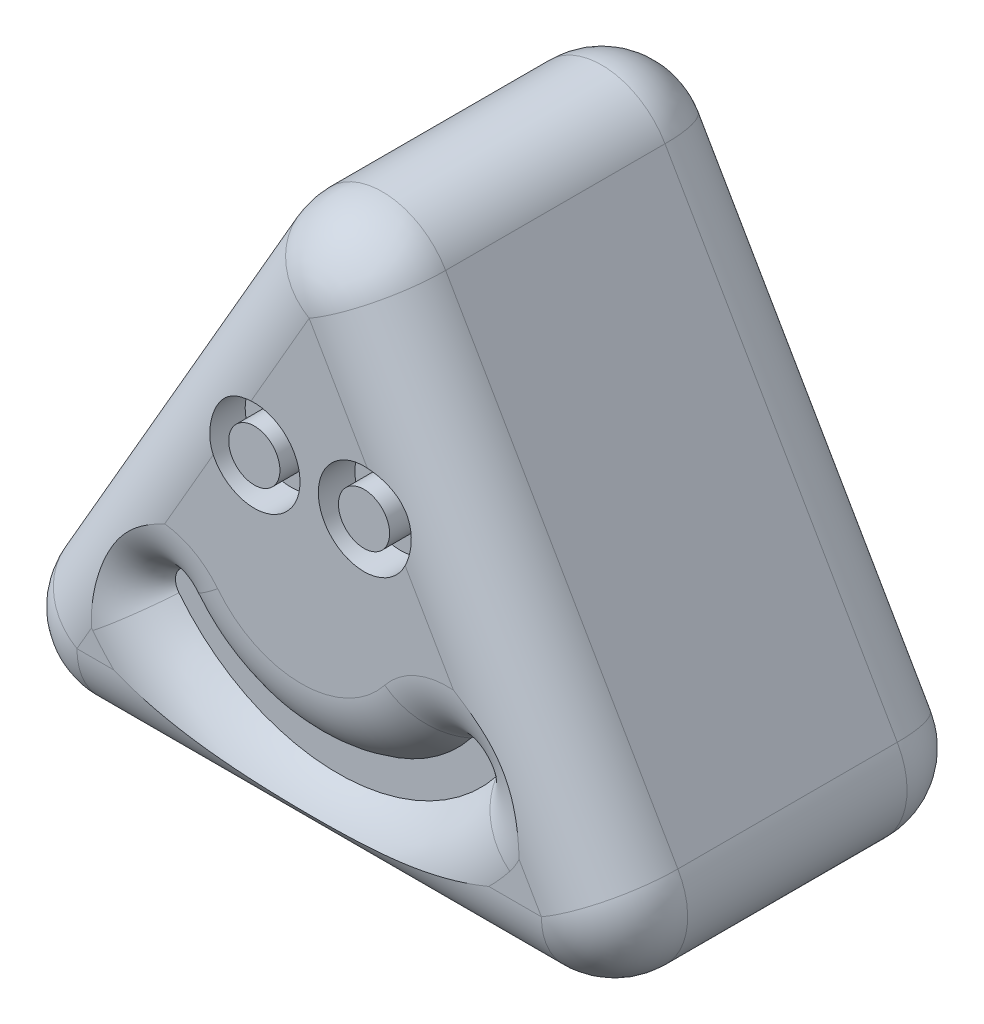
SolidWorks part; units mm, degrees
ref_plane "Front Plane" through (0, 0, 0) normal (0, 0, 1) x (1, 0, 0)
ref_plane "Top Plane" through (0, 0, 0) normal (0, 1, 0) x (1, 0, 0)
ref_plane "Right Plane" through (0, 0, 0) normal (1, 0, 0) x (0, 0, -1)
sketch "Sketch1" plane through (0, 0, 0) normal (0, 0, 1) x (1, 0, 0)
  line L0 (-9.815, -17) -> (9.815, -17)
  line L1 (9.815, -17) -> (0, 0)
  line L2 (0, 0) -> (-9.815, -17)
  point P4 (0, -17)
  dimension "D1" = 17
extrude "Boss-Extrude1" add sketch "Sketch1" along normal blind 10
sketch "Sketch2" plane through (0, 0, 10) normal (0, 0, 1) x (1, 0, 0)
  arc A0 (-4.2097, -13.0055) -> (3.7774, -13.0055) centre (-0.2162, -9.8526) ccw construction
  arc A1 (-4.5598, -13.2819) -> (4.1274, -13.2819) centre (-0.2162, -9.8526) ccw
  arc A2 (-3.8597, -12.7292) -> (3.4273, -12.7292) centre (-0.2162, -9.8526) ccw
  arc A3 (-3.8597, -12.7292) -> (-4.5598, -13.2819) centre (-4.2097, -13.0055) ccw
  arc A4 (4.1274, -13.2819) -> (3.4273, -12.7292) centre (3.7774, -13.0055) ccw
  point P3 (-0.2162, -14.9408)
extrude "Cut-Extrude1" cut sketch "Sketch2" against normal blind 1
fillet "Fillet1" radius 2 13 edges at (9.815, -17, 5) (0, 0, 5) (4.9075, -8.5, 0) (4.9075, -8.5, 10) (0, -17, 10) (-4.9075, -8.5, 10) (-0.2162, -15.3868, 10) (4.0537, -12.6555, 10) (-0.2162, -14.4948, 10) (-4.4861, -12.6555, 10) (-4.9075, -8.5, 0) (-9.815, -17, 5) (0, -17, 0)
sketch "Sketch3" plane through (0, 0, 10) normal (0, 0, 1) x (1, 0, 0)
  line L0 (6.3509, -17) -> (-6.3509, -17) construction
  line L1 (0, -5.6491) -> (0, 5.6491) construction
  circle A0 centre (1.5, -8) radius 1.25
  circle A1 centre (1.5, -8) radius 0.7
  circle A2 centre (-1.5, -8) radius 0.7
  circle A3 centre (-1.5, -8) radius 1.25
  point P5 (0, -17)
  dimension "D1" = 2.5
  dimension "D2" = 1.4
  dimension "D3" = 1.5
  dimension "D4" = 9
extrude "Cut-Extrude2" cut sketch "Sketch3" against normal blind 1 contours A2 | A1 | A3 | A0
sketch "Sketch4" plane through (0, -17, 0) normal (0, -1, 0) x (1, 0, 0)
  line L0 (-4, 5) -> (4, 5) construction
  line L1 (-4, 5.9) -> (4, 5.9)
  line L2 (-4, 4.1) -> (4, 4.1)
  line L4 (6.3509, 2) -> (6.3509, 8) construction
  arc A0 (-4, 5.9) -> (-4, 4.1) centre (-4, 5) ccw
  arc A1 (4, 4.1) -> (4, 5.9) centre (4, 5) ccw
  point P2 (0, 5)
  point P7 (0, 0)
  point P11 (6.3509, 5)
  dimension "D1" = 0.9
  dimension "D2" = 8
extrude "Boss-Extrude2" add sketch "Sketch4" along normal blind 2
